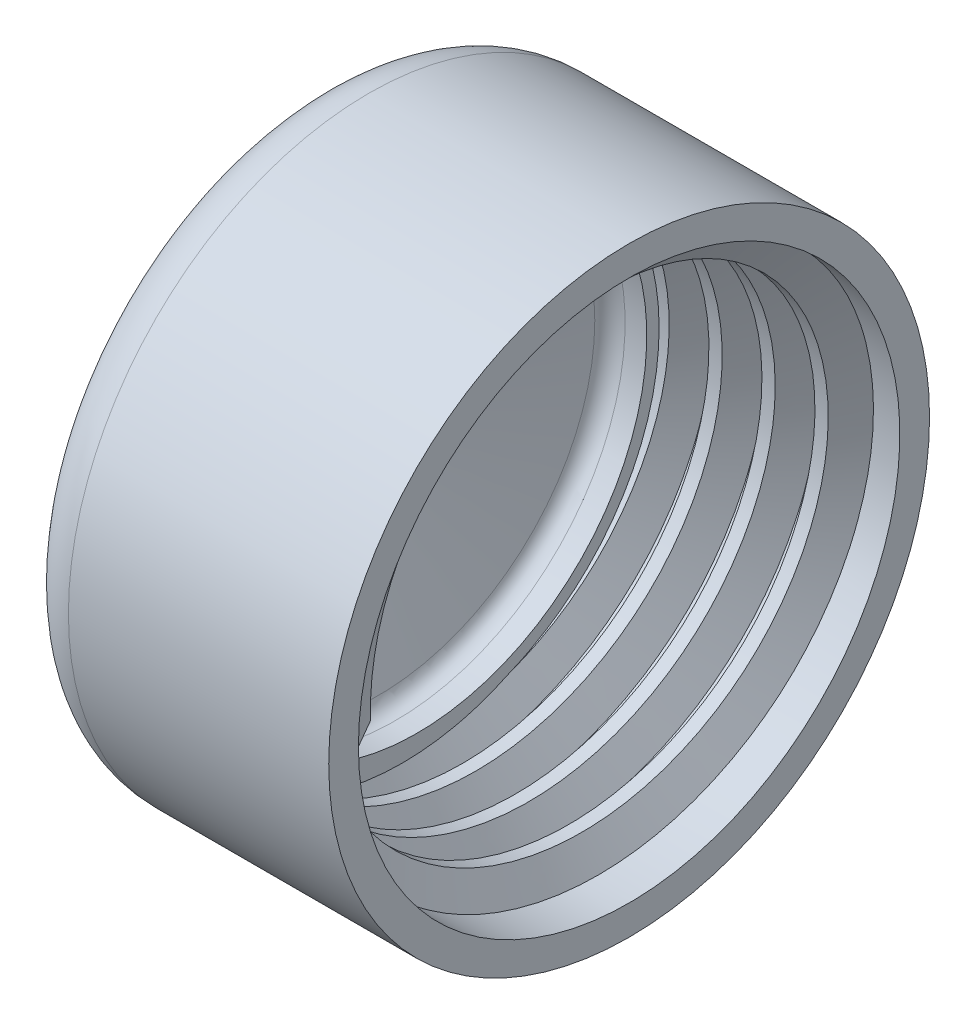
SolidWorks part; units mm, degrees
ref_plane "Front Plane" through (0, 0, 0) normal (0, 0, 1) x (1, 0, 0)
ref_plane "Top Plane" through (0, 0, 0) normal (0, 1, 0) x (1, 0, 0)
ref_plane "Right Plane" through (0, 0, 0) normal (1, 0, 0) x (0, 0, -1)
sketch "Sketch1" plane through (0, 0, 0) normal (0, 1, 0) x (1, 0, 0)
  line L0 (-10, 0) -> (10, 0) construction
  line L1 (12.2685, 17) -> (12.2685, 15.32)
  line L2 (12.2685, 17) -> (0.2685, 17)
  line L8 (-0.9589, 13) -> (0.2685, 13)
  line L9 (-1.9265, 12.2524) -> (-4.7315, 1.5)
  line L10 (-4.7315, 1.5) -> (-6.7315, 1.5)
  line L11 (-6.7315, 1.5) -> (-6.7315, 2.6988)
  line L12 (-6.7315, 2.6988) -> (-5.4623, 2.6988)
  line L14 (0.2685, 17) -> (-2.4623, 17)
  line L15 (-5.4623, 14) -> (-5.4623, 2.6988)
  line L16 (12.2685, 15.32) -> (0.2685, 15.32)
  line L17 (0.2685, 15.32) -> (0.2685, 13)
  arc A0 (-2.4623, 17) -> (-5.4623, 14) centre (-2.4623, 14) ccw
  arc A1 (-0.9589, 13) -> (-1.9265, 12.2524) centre (-0.9589, 12) ccw
  point P2 (0, 0)
  point P17 (-1.7315, 13)
  dimension "D9" = 3
  dimension "D10" = 1
  dimension "D1" = 20
  dimension "D2" = 12
  dimension "D3" = 1.68
  dimension "D4" = 34
  dimension "D5" = 26
  dimension "D6" = 3
  dimension "D7" = 1.5
  dimension "D8" = 2
  dimension "D11" = 12
revolve "Revolve1" add sketch "Sketch1" angle 360 about L0
thread "Thread1" pitch 3 method extrude profile "Thread Profile2" start angle 0, offset 0, length 12, pitch 3, diameter 30.64
ref_plane "Plane2" through (12.2685, 0, 15.32) normal (0, -1, 0) x (0, 0, 1)
sketch "Thread Profile2" plane through (12.2685, 0, 15.32) normal (0, -1, 0) x (0, 0, 1)
  line L0 (0, 0) -> (0, 3) construction
  line L11 (0, 0) -> (0, 2.625)
  line L12 (0, 2.625) -> (-1.6238, 1.6875)
  line L13 (-1.6238, 1.6875) -> (-1.6238, 0.9375)
  line L15 (-1.6238, 0.9375) -> (0, 0)
  line L17 (-1.6238, 1.3125) -> (0, 1.3125) construction
  point P2 (0, 0)
  dimension "Pitch" = 3
  dimension "Profile_Angle" = 60
  dimension "Profile_Land" = 0.75
  dimension "Profile_Height" = 1.6238
